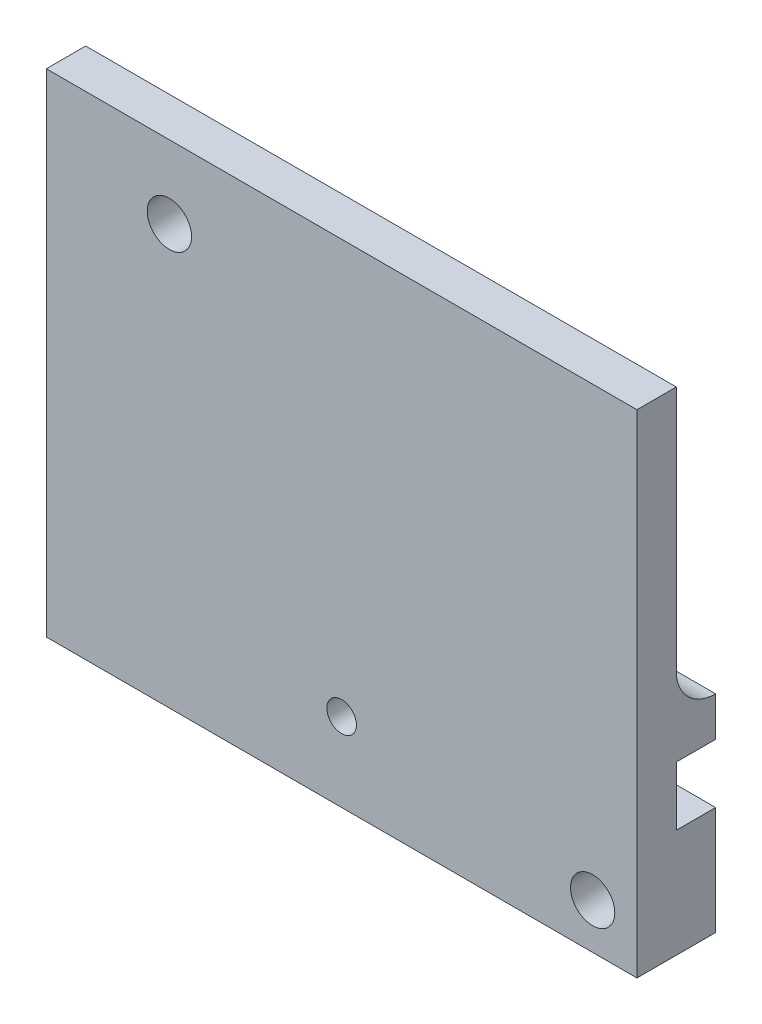
SolidWorks part; units mm, degrees
ref_plane "Płaszczyzna przednia" through (0, 0, 0) normal (0, 0, 1) x (1, 0, 0)
ref_plane "Płaszczyzna górna" through (0, 0, 0) normal (0, 1, 0) x (1, 0, 0)
ref_plane "Płaszczyzna prawa" through (0, 0, 0) normal (1, 0, 0) x (0, 0, -1)
sketch "Sketch1" plane through (0, 0, 0) normal (0, 0, 1) x (1, 0, 0)
  line L1 (0, 0) -> (60, 0)
  line L2 (0, 0) -> (0, 50)
  line L3 (0, 50) -> (60, 50)
  line L4 (60, 0) -> (60, 50)
  line L5 (0, 0) -> (60, 50) construction
  line L6 (0, 50) -> (60, 0) construction
  point P4 (30, 25)
  dimension "D1" = 60
  dimension "D2" = 50
extrude "Boss-Extrude1" add sketch "Sketch1" along normal blind 4
sketch "Sketch2" plane through (0, 0, 0) normal (0, 0, -1) x (-1, 0, 0)
  line L0 (0, 50) -> (0, 0) construction
  line L1 (0, 21) -> (-60, 21)
  line L2 (0, 21) -> (0, 17)
  line L3 (0, 17) -> (-60, 17)
  line L4 (-60, 21) -> (-60, 17)
  line L5 (0, 21) -> (-60, 17) construction
  line L6 (0, 17) -> (-60, 21) construction
  line L7 (-60, 0) -> (-60, 50) construction
  line L9 (0, 0) -> (-60, 0) construction
  point P4 (-30, 19)
  dimension "D1" = 17
  dimension "D2" = 4
extrude "Boss-Extrude2" add sketch "Sketch2" along normal blind 4
fillet "Fillet1" radius 4 1 edges at (30, 21, 0)
hole_wizard "Ø3.0 (3) Diameter Hole1" positions "Sketch4" profile "Sketch5" hole size "Ø3.0" standard "ANSI Metric"
sketch "Sketch4" plane through (0, 0, 4) normal (0, 0, 1) x (1, 0, 0)
  point P0 (30, 8)
sketch "Sketch5" plane through (30, 8, 4) normal (1, 0, 0) x (0, -1, 0)
  line L0 (0, 0) -> (0, 12.9013)
  line L1 (0, 12.9013) -> (1.5, 12)
  line L2 (1.5, 12) -> (1.5, 0)
  line L5 (1.5, 0) -> (0, 0)
  line L10 (0, 12.9013) -> (-1.5, 12) construction
  line L11 (0, -6.35) -> (0, 107.95) construction
  dimension "Hole Dia." = 3
  dimension "Hole Depth" = 12
  dimension "Drill Angle" = 118
sketch "Sketch6" plane through (0, 0, 0) normal (0, 0, -1) x (-1, 0, 0)
  line L0 (0, 0) -> (0, 11)
  line L1 (0, 17) -> (0, 0) construction
  line L2 (-10, 11) -> (0, 11) construction
  line L3 (0, 11) -> (-21, 11)
  line L4 (-27, 5) -> (-27, 0)
  line L5 (0, 0) -> (-60, 0) construction
  line L6 (-27, 0) -> (0, 0)
  line L7 (-33, 5) -> (-33, 0)
  line L8 (-33, 5) -> (-33, -14) construction
  line L9 (-33, 0) -> (-60, 0)
  line L10 (-60, 0) -> (-60, 11)
  line L11 (-60, 0) -> (-60, 17) construction
  line L12 (-60, 11) -> (-39, 11)
  arc A0 (-21, 11) -> (-27, 5) centre (-21, 5) ccw
  arc A1 (-33, 5) -> (-39, 11) centre (-39, 5) ccw
extrude "Boss-Extrude3" add sketch "Sketch6" along normal blind 4
sketch "Sketch3" plane through (0, 0, 4) normal (0, 0, 1) x (1, 0, 0)
  circle A0 centre (12.5, 42.6) radius 2.25
  circle A1 centre (55.5, 4.6) radius 2.25
  dimension "D1" = 4.5
  dimension "D2" = 4.5
extrude "Cut-Extrude1" cut sketch "Sketch3" against normal through all
